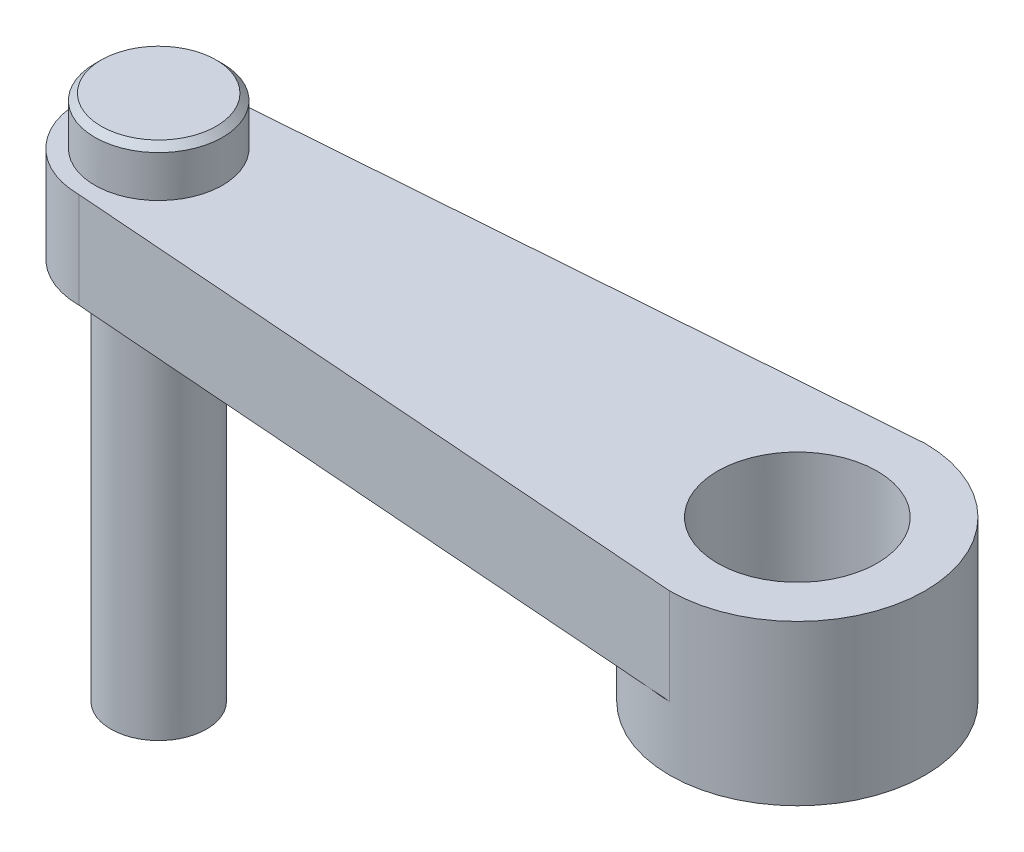
SolidWorks part; units mm, degrees
ref_plane "Front Plane" through (0, 0, 0) normal (0, 0, 1) x (1, 0, 0)
ref_plane "Top Plane" through (0, 0, 0) normal (0, 1, 0) x (1, 0, 0)
ref_plane "Right Plane" through (0, 0, 0) normal (1, 0, 0) x (0, 0, -1)
sketch "Sketch3" plane through (0, 0, 0) normal (0, 1, 0) x (1, 0, 0)
  line L0 (0, 0) -> (20, -1.5)
  line L1 (0, 5) -> (20, 6.5)
  arc A0 (20, -1.5) -> (20, 6.5) centre (20, 2.5) ccw
  arc A1 (0, 0) -> (0, 5) centre (0, 2.5) cw
  circle A2 centre (0, 2.5) radius 1.5
  circle A3 centre (20, 2.5) radius 2.5
  dimension "D1" = 3
  dimension "D2" = 5
  dimension "D3" = 20
  dimension "D5" = 4
  dimension "D4" = 2.5
extrude "Boss-Extrude1" add sketch "Sketch3" along normal blind 3
sketch "Sketch4" plane through (0, 0, 0) normal (0, -1, 0) x (1, 0, 0)
  circle A0 centre (20, -2.5) radius 4
  circle A1 centre (20, -2.5) radius 2.5 construction
  circle A2 centre (20, -2.5) radius 2.5
  dimension "D1" = 8
extrude "Boss-Extrude2" add sketch "Sketch4" along normal blind 2
sketch "Sketch5" plane through (0, 3, 0) normal (0, 1, 0) x (1, 0, 0)
  circle A0 centre (0, 2.5) radius 1.5
extrude "Boss-Extrude3" add sketch "Sketch5" against normal blind 15
sketch "Sketch6" plane through (0, 3, 0) normal (0, 1, 0) x (1, 0, 0)
  circle A0 centre (0, 2.5) radius 2
  arc A1 (0, 5) -> (0, 0) centre (0, 2.5) ccw construction
  dimension "D1" = 4
extrude "Boss-Extrude4" add sketch "Sketch6" along normal blind 1.5
chamfer "Chamfer1" distance 0.2 angle 45 1 edges at (0, 4.5, -0.5)
